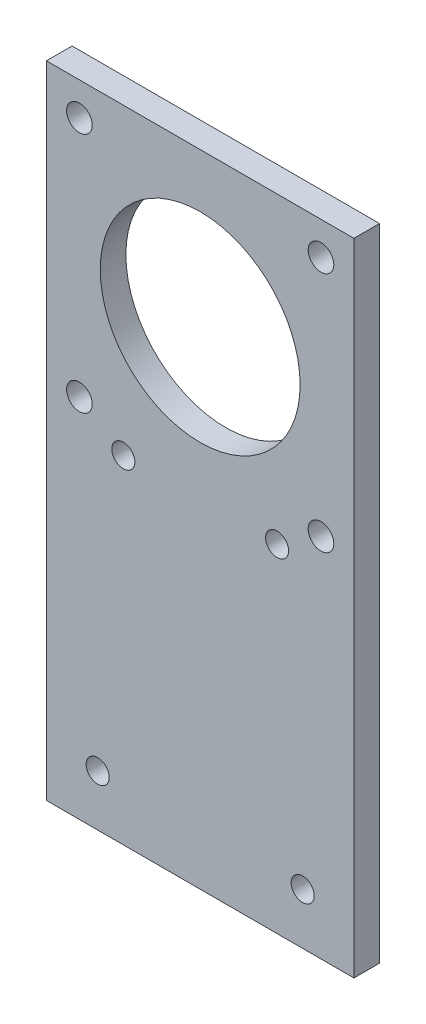
SolidWorks part; units mm, degrees
ref_plane "정면" through (0, 0, 0) normal (0, 0, 1) x (1, 0, 0)
ref_plane "윗면" through (0, 0, 0) normal (0, 1, 0) x (1, 0, 0)
ref_plane "우측면" through (0, 0, 0) normal (1, 0, 0) x (0, 0, -1)
sketch "스케치1" plane through (0, 0, 0) normal (0, 0, 1) x (1, 0, 0)
  line L1 (-30, 62.5) -> (30, 62.5)
  line L2 (-30, 62.5) -> (-30, -62.5)
  line L3 (-30, -62.5) -> (30, -62.5)
  line L4 (30, 62.5) -> (30, -62.5)
  line L5 (-30, 62.5) -> (30, -62.5) construction
  line L6 (-30, -62.5) -> (30, 62.5) construction
  point P0 (0, 0)
  dimension "D1" = 60
  dimension "D2" = 125
extrude "보스-돌출1" add sketch "스케치1" along normal blind 5
sketch "스케치4" plane through (0, 0, 0) normal (0, 0, -1) x (-1, 0, 0)
  line L3 (-30, 62.5) -> (30, 62.5) construction
  line L4 (30, 62.5) -> (30, -62.5) construction
  circle A0 centre (0, 32.5) radius 19.5
  dimension "D1" = 39
  dimension "D3" = 30
  dimension "D2" = 30
extrude "컷-돌출2" cut sketch "스케치4" against normal blind 10
sketch "스케치2" plane through (0, 0, 5) normal (0, 0, 1) x (1, 0, 0)
  circle A10 centre (-23.57, 56.07) radius 5.8
  circle A11 centre (-23.57, 56.07) radius 2.5
  circle A12 centre (23.57, 56.07) radius 5.8
  circle A13 centre (23.57, 56.07) radius 2.5
  circle A14 centre (-23.57, 8.93) radius 5.8
  circle A15 centre (-23.57, 8.93) radius 2.5
  circle A16 centre (23.57, 8.93) radius 5.8
  circle A17 centre (23.57, 8.93) radius 2.5
  circle A18 centre (0, 32.5) radius 19.5 construction
  dimension "D3" = 5
  dimension "D4" = 11.6
  dimension "D5" = 5
  dimension "D8" = 11.6
  dimension "D9" = 11.6
  dimension "D10" = 47.14
  dimension "D11" = 23.57
  dimension "D12" = 23.57
  dimension "D13" = 23.57
  dimension "D2" = 11.6
  dimension "D6" = 5
  dimension "D7" = 5
  dimension "D16" = 23.57
  dimension "D17" = 47.14
extrude "컷-돌출1" cut sketch "스케치2" against normal blind 5 contours A13 | A17 | A15 | A11 region at (23.57, 56.07, 5) region at (-23.57, 8.93, 5) region at (23.57, 8.93, 5)
hole_wizard "M4 여유 구멍1" positions "스케치6" profile "스케치7" hole size "M4" standard "KS" end condition through all
sketch "스케치6" plane through (0, 0, 0) normal (0, 0, -1) x (-1, 0, 0)
  line L0 (-30, -62.5) -> (-30, 62.5) construction
  line L1 (-30, 62.5) -> (30, 62.5) construction
  line L2 (30, 62.5) -> (30, -62.5) construction
  line L3 (30, -62.5) -> (-30, -62.5) construction
  point P0 (15, 3.3)
  point P2 (-15, 3.3)
  point P4 (-20, -52.5)
  point P6 (20, -52.5)
  dimension "D1" = 15
  dimension "D2" = 59.2
  dimension "D3" = 59.2
  dimension "D4" = 15
  dimension "D5" = 10
  dimension "D6" = 10
  dimension "D7" = 10
  dimension "D8" = 10
sketch "스케치7" plane through (-15, 3.3, 0) normal (1, 0, 0) x (0, 1, 0)
  line L0 (0, 0) -> (0, 5)
  line L1 (0, 5) -> (2.25, 5)
  line L2 (2.25, 5) -> (2.25, 0)
  line L5 (2.25, 0) -> (0, 0)
  line L11 (0, -6.35) -> (0, 107.95) construction
  dimension "관통 구멍 지름" = 4.5
  dimension "관통 구멍 깊이" = 5
